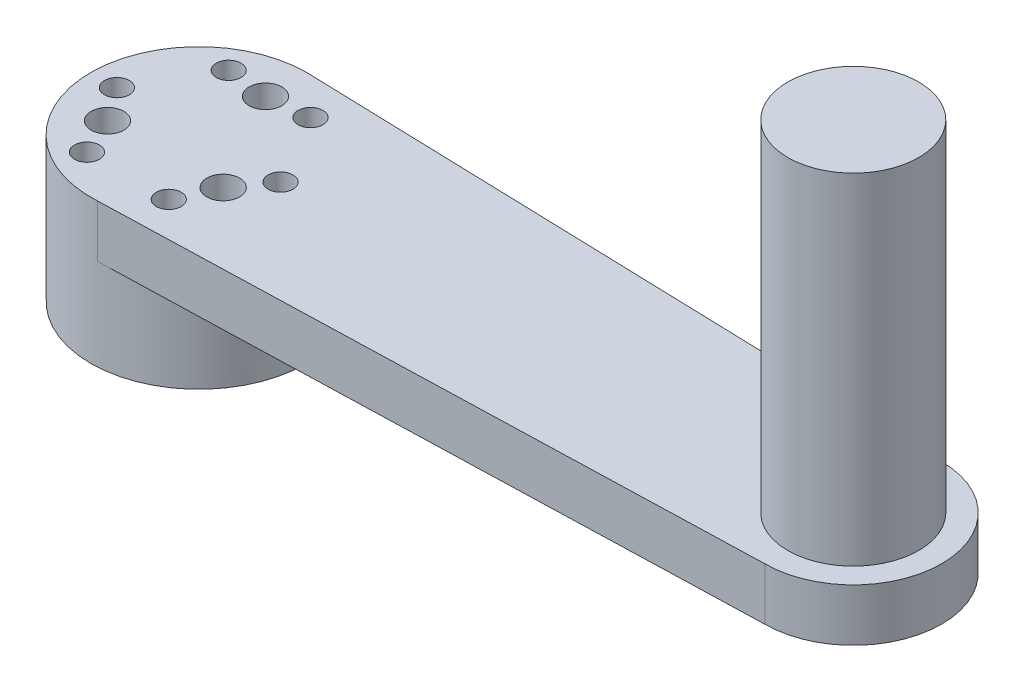
SolidWorks part; units mm, degrees
ref_plane "前视基准面" through (0, 0, 0) normal (0, 0, 1) x (1, 0, 0)
ref_plane "上视基准面" through (0, 0, 0) normal (0, 1, 0) x (1, 0, 0)
ref_plane "右视基准面" through (0, 0, 0) normal (1, 0, 0) x (0, 0, -1)
other "Configuration Table"
sketch "草图1" plane through (0, 0, 0) normal (0, 1, 0) x (1, 0, 0)
  line L0 (0, 0) -> (0, 12.5) construction
  line L1 (0, 0) -> (0, -12.5) construction
  line L2 (0, 0) -> (-6.25, 10.8253)
  line L3 (0, 0) -> (100, 0)
  line L4 (100, -13.5) -> (0, -16.5)
  line L5 (100, 13.5) -> (0, 16.5)
  circle A0 centre (0, 0) radius 10.2
  circle A1 centre (0, 0) radius 12.5
  circle A4 centre (0, 0) radius 16.5
  circle A7 centre (100, 0) radius 13.5
  circle A8 centre (100, 0) radius 10
  dimension "D1" = 20.4
  dimension "D2" = 25
  dimension "D3" = 100
  dimension "D4" = 30
  dimension "D5" = 33
  dimension "D6" = 27
  dimension "D7" = 20
extrude "凸台-拉伸1" add sketch "草图1" along normal blind 8 contours A4
sketch "草图4" plane through (0, 8, 0) normal (0, 1, 0) x (1, 0, 0)
  line L0 (0, -10.2) -> (0, 10.2) construction
  line L1 (0, 0) -> (-6.25, 10.8253)
  circle A0 centre (0, 0) radius 10.2
  circle A1 centre (0, 0) radius 12.5
  circle A2 centre (0, 10.2) radius 2.5
  circle A3 centre (-6.25, 10.8253) radius 1.9
  circle A4 centre (6.25, 10.8253) radius 1.9
  circle A5 centre (12.5, 0) radius 1.9
  circle A6 centre (6.25, -10.8253) radius 1.9
  circle A7 centre (-6.25, -10.8253) radius 1.9
  circle A8 centre (-12.5, 0) radius 1.9
  circle A9 centre (8.8335, -5.1) radius 2.5
  circle A10 centre (-8.8335, -5.1) radius 2.5
  point P23 (0, 0)
  point P28 (0, 0)
  dimension "D1" = 20.4
  dimension "D2" = 25
  dimension "D4" = 3.8
  dimension "D5" = 5
  dimension "D3" = 30
  dimension "D6" = 6
  dimension "D7" = 3
extrude "切除-拉伸1" cut sketch "草图4" against normal through all and the other way through all contours A8 | A3 | A2 | A10 | A7 | A6 | A9 | A5 | A4
extrude "凸台-拉伸2" add sketch "草图1<3>" along normal blind 8 contours A7 L3 A4 L4 | A7 L5 A4 L3 | A8 A7 region at (50.3121, 0, -7.8476) region at (50.3121, 0, 7.8476) region at (90.7241, 0, -9.2759)
sketch "草图1<3>" plane through (0, 0, 0) normal (0, 1, 0) x (1, 0, 0) same geometry as "草图1"
extrude "凸台-拉伸3" add sketch "草图1<4>" along normal blind 60 contours A8 region at (100, 0, -9.7172)
sketch "草图1<4>" plane through (0, 0, 0) normal (0, 1, 0) x (1, 0, 0) same geometry as "草图1"
sketch "草图5" plane through (0, 0, 0) normal (0, -1, 0) x (1, 0, 0)
  circle A0 centre (0, 0) radius 16.5
  dimension "D1" = 33
extrude "凸台-拉伸4" add sketch "草图5" along normal blind 14
sketch "草图6" plane through (0, -14, 0) normal (0, -1, 0) x (1, 0, 0)
  circle A0 centre (-8.8335, 5.1) radius 2.5 construction
  circle A1 centre (-12.5, 0) radius 1.9 construction
  circle A2 centre (-6.25, -10.8253) radius 1.9 construction
  circle A3 centre (0, -10.2) radius 2.5 construction
  circle A4 centre (6.25, -10.8253) radius 1.9 construction
  circle A5 centre (12.5, 0) radius 1.9 construction
  circle A6 centre (8.8335, 5.1) radius 2.5 construction
  circle A7 centre (6.25, 10.8253) radius 1.9 construction
  circle A8 centre (-6.25, 10.8253) radius 1.9 construction
  circle A9 centre (-8.8335, 5.1) radius 2.5
  circle A10 centre (-12.5, 0) radius 1.9
  circle A11 centre (-6.25, -10.8253) radius 1.9
  circle A12 centre (0, -10.2) radius 2.5
  circle A13 centre (6.25, -10.8253) radius 1.9
  circle A14 centre (12.5, 0) radius 1.9
  circle A15 centre (8.8335, 5.1) radius 2.5
  circle A16 centre (6.25, 10.8253) radius 1.9
  circle A17 centre (-6.25, 10.8253) radius 1.9
extrude "切除-拉伸2" cut sketch "草图6" against normal blind 14
